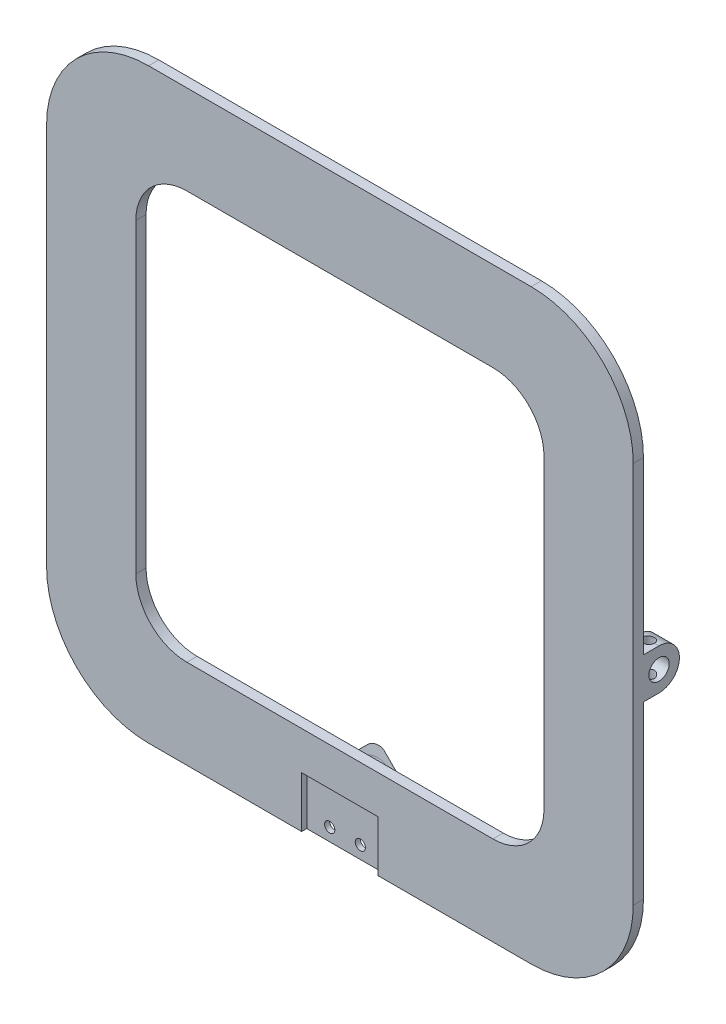
SolidWorks part; units mm, degrees
ref_plane "Płaszczyzna przednia" through (0, 0, 0) normal (0, 0, 1) x (1, 0, 0)
ref_plane "Płaszczyzna górna" through (0, 0, 0) normal (0, 1, 0) x (1, 0, 0)
ref_plane "Płaszczyzna prawa" through (0, 0, 0) normal (1, 0, 0) x (0, 0, -1)
sketch "Szkic1" plane through (0, 0, 0) normal (0, 0, 1) x (1, 0, 0)
  line L0 (0, -57.5) -> (115, -57.5) construction
  line L1 (0, 0) -> (115, 0)
  line L2 (0, 0) -> (0, -115)
  line L3 (0, -115) -> (115, -115)
  line L4 (115, 0) -> (115, -115)
  dimension "D1" = 115
  dimension "D2" = 115
extrude "Dodanie-wyciągnięcie1" add sketch "Szkic1" along normal blind 2
sketch "Szkic3" plane through (115, 0, 0) normal (1, 0, 0) x (0, 0, -1)
  line L0 (0, -115) -> (0, 0) construction
  line L1 (0, -53.5) -> (3.0506, -53.5)
  line L2 (0, -53.5) -> (0, -61.5)
  line L3 (0, -61.5) -> (3.0506, -61.5)
  line L6 (-2, -115) -> (0, -115) construction
  arc A0 (3.0506, -61.5) -> (3.0506, -53.5) centre (3.0506, -57.5) ccw
  dimension "D1" = 8
  dimension "D2" = 53.5
extrude "Dodanie-wyciągnięcie2" add sketch "Szkic3" against normal blind 4
ref_plane "Płaszczyzna1" through (57.5, 0, 0) normal (1, 0, 0) x (0, 0, -1)
mirror "Lustro1" about plane through (57.5, 0, 0) normal (1, 0, 0) of "Dodanie-wyciągnięcie2"
sketch "Szkic5" plane through (115, 0, 0) normal (1, 0, 0) x (0, 0, -1)
  circle A0 centre (3.0506, -57.5) radius 2
  arc A1 (3.0506, -61.5) -> (3.0506, -53.5) centre (3.0506, -57.5) ccw construction
  dimension "D1" = 4
extrude "Wytnij-wyciągnięcie1" cut sketch "Szkic5" against normal through all
sketch "Szkic6" plane through (0, 0, 2) normal (0, 0, 1) x (1, 0, 0)
  line L0 (0, 0) -> (0, -115) construction
  line L2 (0, -115) -> (115, -115) construction
  circle A0 centre (54.5, -112.5) radius 1
  circle A1 centre (60.5, -112.5) radius 1
  dimension "D1" = 2
  dimension "D2" = 2
  dimension "D5" = 2.5
  dimension "D6" = 2.5
  dimension "D3" = 6
  dimension "D4" = 54.5
extrude "Wytnij-wyciągnięcie2" cut sketch "Szkic6" against normal blind 10
fillet "Zaokrąglenie1" radius 20 4 edges at (0, -115, 1) (115, -115, 1) (0, 0, 1) (115, 0, 1)
sketch "Szkic7" plane through (0, 0, 2) normal (0, 0, 1) x (1, 0, 0)
  line L0 (20, -115) -> (95, -115) construction
  line L1 (50, -115) -> (65, -115)
  line L2 (50, -115) -> (50, -105)
  line L3 (50, -105) -> (65, -105)
  line L4 (65, -115) -> (65, -105)
  line L5 (0, -20) -> (0, -95) construction
  dimension "D1" = 10
  dimension "D2" = 15
  dimension "D3" = 50
extrude "Wytnij-wyciągnięcie3" cut sketch "Szkic7" against normal blind 1
sketch "Szkic8" plane through (0, 0, 0) normal (0, 0, -1) x (-1, 0, 0)
  line L0 (0, -20) -> (0, -53.5) construction
  line L1 (-87.5, -97.5) -> (-27.5, -97.5)
  line L2 (-97.5, -87.5) -> (-97.5, -27.5)
  line L3 (-87.5, -17.5) -> (-27.5, -17.5)
  line L4 (-17.5, -87.5) -> (-17.5, -27.5)
  line L5 (-97.5, -97.5) -> (-17.5, -17.5) construction
  line L6 (-97.5, -17.5) -> (-17.5, -97.5) construction
  line L7 (-95, 0) -> (-20, 0) construction
  arc A0 (-87.5, -97.5) -> (-97.5, -87.5) centre (-87.5, -87.5) cw
  arc A1 (-27.5, -97.5) -> (-17.5, -87.5) centre (-27.5, -87.5) ccw
  arc A2 (-27.5, -17.5) -> (-17.5, -27.5) centre (-27.5, -27.5) cw
  arc A3 (-97.5, -27.5) -> (-87.5, -17.5) centre (-87.5, -27.5) cw
  point P0 (-57.5, -57.5)
  dimension "D5" = 10
  dimension "D1" = 80
  dimension "D2" = 80
  dimension "D3" = 17.5
  dimension "D4" = 17.5
extrude "Wytnij-wyciągnięcie4" cut sketch "Szkic8" against normal blind 10
sketch "Szkic9" plane through (0, -53.5, 0) normal (0, 1, 0) x (1, 0, 0)
  line L0 (4, 3.0506) -> (0, 3.0506) construction
  circle A0 centre (2, 3.0506) radius 1.1
extrude "Wytnij-wyciągnięcie5" cut sketch "Szkic9" against normal through all
sketch "Szkic10" plane through (0, -53.5, 0) normal (0, 1, 0) x (1, 0, 0)
  line L0 (111, 3.0506) -> (115, 3.0506) construction
  circle A0 centre (113, 3.0506) radius 1.1
extrude "Wytnij-wyciągnięcie6" cut sketch "Szkic10" against normal blind 10
sketch "Szkic13" plane through (0, 0, 0) normal (0, 0, -1) x (-1, 0, 0)
  line L0 (-57.5, -115) -> (-57.5, -97.5) construction
  line L1 (-20, -115) -> (-95, -115) construction
  line L2 (-87.5, -97.5) -> (-27.5, -97.5) construction
  line L3 (-57.5, -106.25) -> (-66.25, -115) construction
  line L5 (-53.0806, -103.5983) -> (-60.1517, -110.6694)
  line L6 (-53.0806, -103.5983) -> (-54.8483, -101.8306)
  line L7 (-60.1517, -110.6694) -> (-61.9194, -108.9017)
  line L8 (-54.8483, -101.8306) -> (-61.9194, -108.9017)
  line L9 (-53.0806, -103.5983) -> (-61.9194, -108.9017) construction
  line L10 (-60.1517, -110.6694) -> (-54.8483, -101.8306) construction
  dimension "D1" = 10
  dimension "D2" = 2.5
  dimension "D3" = 45
extrude "Dodanie-wyciągnięcie4" add sketch "Szkic13" along normal blind 8
sketch "Szkic14" plane through (-25.2589, -25.2589, 0) normal (-0.7071, -0.7071, 0) x (-0.7071, 0.7071, 0)
  line L0 (-120.7887, 0) -> (-110.7887, 0) construction
  line L1 (-112.7887, 0) -> (-118.7887, 0)
  line L2 (-112.7887, 0) -> (-112.7887, 6)
  line L3 (-112.7887, 6) -> (-118.7887, 6)
  line L4 (-118.7887, 0) -> (-118.7887, 6)
  line L5 (-120.7887, 8) -> (-110.7887, 8) construction
  line L6 (-110.7887, 8) -> (-110.7887, 0) construction
  line L7 (-120.7887, 8) -> (-120.7887, 0) construction
  dimension "D1" = 2
  dimension "D2" = 2
  dimension "D3" = 2
extrude "Wytnij-wyciągnięcie8" cut sketch "Szkic14" against normal blind 8
fillet "Zaokrąglenie3" radius 2 4 edges at (59.6213, -108.3713, -6) (55.3787, -104.1287, -6) (61.0355, -109.7855, -8) (53.9645, -102.7145, -8)
fillet "Zaokrąglenie4" radius 1 10 edges at (56.2626, -103.2448, -2) (56.6768, -103.659, -5.4142) (58.3839, -105.3661, -6) (60.091, -107.0732, -5.4142) (54.4948, -105.0126, -2) (54.909, -105.4268, -5.4142) (56.6161, -107.1339, -6) (58.3232, -108.841, -5.4142) (60.5052, -107.4874, -2) (58.7374, -109.2552, -2)
sketch "Szkic15" plane through (0, 0, 0) normal (0, 0, -1) x (-1, 0, 0)
  line L0 (-109.1421, -109.1421) -> (-95, -95) construction
  line L1 (-104.6976, -106.4654) -> (-106.4654, -104.6976)
  line L2 (-104.6976, -106.4654) -> (-97.6265, -99.3943)
  line L3 (-106.4654, -104.6976) -> (-99.3943, -97.6265)
  line L4 (-97.6265, -99.3943) -> (-99.3943, -97.6265)
  line L5 (-104.6976, -106.4654) -> (-99.3943, -97.6265) construction
  line L6 (-106.4654, -104.6976) -> (-97.6265, -99.3943) construction
  arc A0 (-115, -95) -> (-95, -115) centre (-95, -95) ccw construction
  point P12 (-102.0459, -102.0459)
  dimension "D1" = 10
  dimension "D2" = 2.5
  dimension "D3" = 0
  dimension "805" = 8.5
extrude "Dodanie-wyciągnięcie5" add sketch "Szkic15" along normal blind 8
sketch "Szkic16" plane through (-0.8839, -0.8839, 0) normal (-0.7071, -0.7071, 0) x (-0.7071, 0.7071, 0)
  line L0 (-149.3148, 0) -> (-139.3148, 0) construction
  line L1 (-149.3148, 8) -> (-139.3148, 8) construction
  line L2 (-147.3148, 6) -> (-141.3148, 6)
  line L3 (-147.3148, 6) -> (-147.3148, 0)
  line L4 (-147.3148, 0) -> (-141.3148, 0)
  line L5 (-141.3148, 6) -> (-141.3148, 0)
  line L6 (-149.3148, 8) -> (-149.3148, 0) construction
  line L7 (-139.3148, 8) -> (-139.3148, 0) construction
  dimension "D1" = 2
  dimension "D2" = 2
  dimension "D3" = 2
extrude "Wytnij-wyciągnięcie9" cut sketch "Szkic16" against normal blind 8
fillet "Zaokrąglenie5" radius 2 4 edges at (99.9246, -99.9246, -6) (104.1673, -104.1673, -6) (98.5104, -98.5104, -8) (105.5815, -105.5815, -8)
fillet "Zaokrąglenie6" radius 1 10 edges at (100.8085, -99.0407, -2) (101.2227, -99.455, -5.4142) (102.9298, -101.1621, -6) (105.0511, -103.2834, -2) (99.0407, -100.8085, -2) (99.455, -101.2227, -5.4142) (101.1621, -102.9298, -6) (102.8692, -104.6369, -5.4142) (104.6369, -102.8692, -5.4142) (103.2834, -105.0511, -2)
pattern_linear "Szyk liniowy1" count 2 spacing 45 along (0, 1, 0) of "Wytnij-wyciągnięcie9", "Dodanie-wyciągnięcie5", "Zaokrąglenie5", "Zaokrąglenie6"
